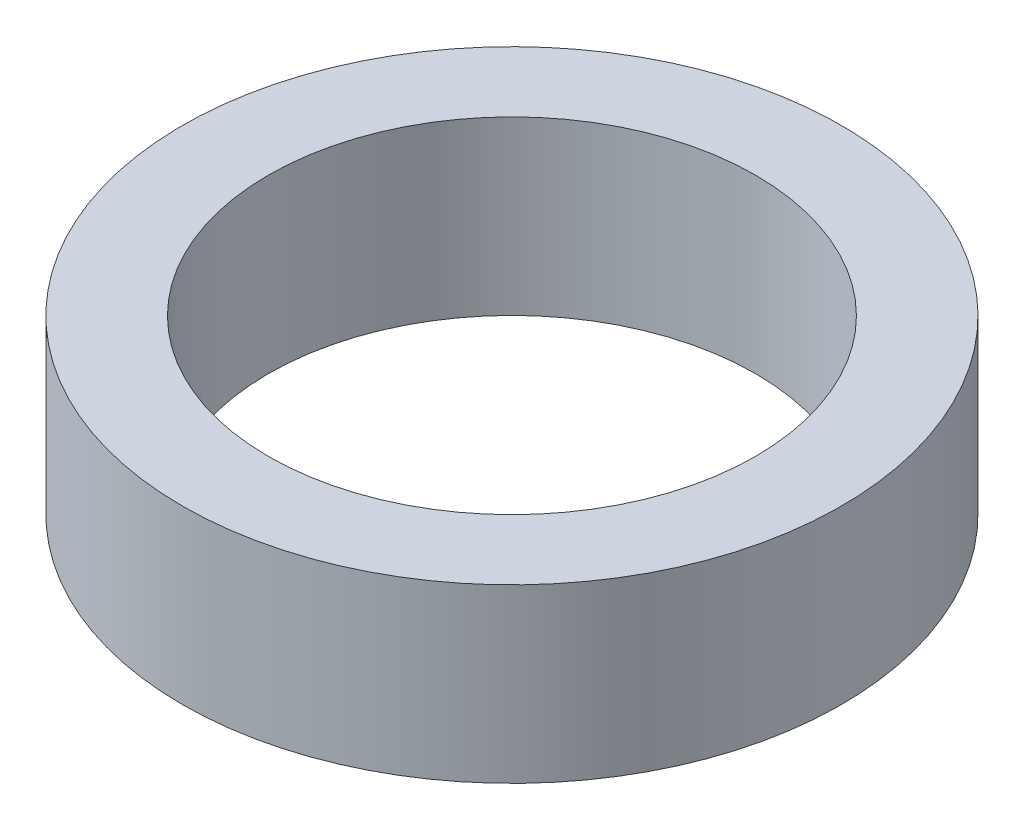
SolidWorks part; units mm, degrees
ref_plane "Front Plane" through (0, 0, 0) normal (0, 0, 1) x (1, 0, 0)
ref_plane "Top Plane" through (0, 0, 0) normal (0, 1, 0) x (1, 0, 0)
ref_plane "Right Plane" through (0, 0, 0) normal (1, 0, 0) x (0, 0, -1)
sketch "Sketch1" plane through (0, 0, 0) normal (0, 1, 0) x (1, 0, 0)
  circle A0 centre (0, 0) radius 57.5
  dimension "FLANGE_OD" = 115
extrude "Boss-Extrude1" add sketch "Sketch1" along normal blind 30
sketch "Sketch2" plane through (0, 0, 0) normal (0, 1, 0) x (1, 0, 0)
  circle A0 centre (0, 0) radius 42.5
  dimension "BORE_D" = 85
extrude "Cut-Extrude1" cut sketch "Sketch2" along normal through all
sketch "Sketch3" plane through (0, 30, 0) normal (0, 1, 0) x (1, 0, 0)
  circle A0 centre (0, 0) radius 25.137 construction
  circle A1 centre (-25.137, 0) radius 1.91
  dimension "BOLT_D" = 3.82
  dimension "BOLT_PCD" = 50.274
extrude "Cut-Extrude2" cut sketch "Sketch3" against normal blind 28.6024 rebuild error yes
pattern_circular "CirPattern1" count 3 over 360 rebuild error yes
